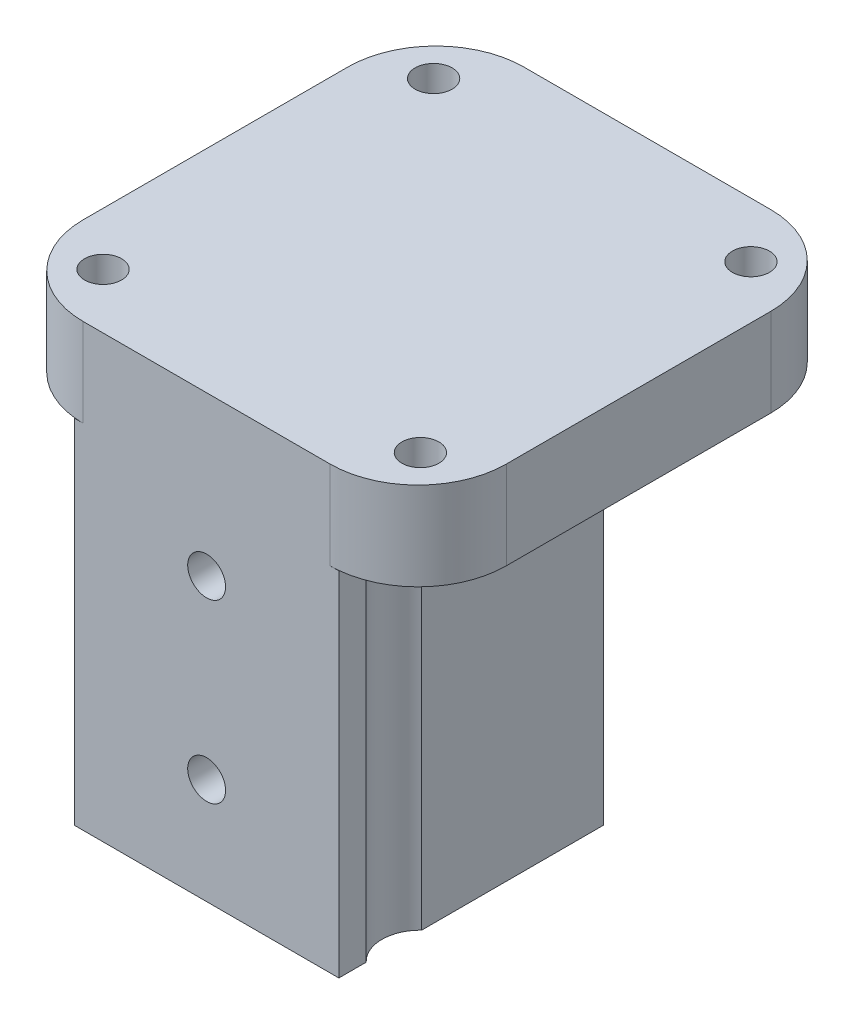
SolidWorks part; units mm, degrees
ref_plane "Front Plane" through (0, 0, 0) normal (0, 0, 1) x (1, 0, 0)
ref_plane "Top Plane" through (0, 0, 0) normal (0, 1, 0) x (1, 0, 0)
ref_plane "Right Plane" through (0, 0, 0) normal (1, 0, 0) x (0, 0, -1)
sketch "Sketch1" plane through (0, 0, 0) normal (0, 1, 0) x (1, 0, 0)
  line L1 (-14, 25) -> (14, 25)
  line L2 (-24, 15) -> (-24, -15)
  line L3 (-14, -25) -> (14, -25)
  line L4 (24, 15) -> (24, -15)
  line L5 (-24, 25) -> (24, -25) construction
  line L6 (-24, -25) -> (24, 25) construction
  arc A0 (-24, -15) -> (-14, -25) centre (-14, -15) ccw
  arc A1 (14, -25) -> (24, -15) centre (14, -15) ccw
  arc A2 (14, 25) -> (24, 15) centre (14, 15) cw
  arc A3 (-14, 25) -> (-24, 15) centre (-14, 15) ccw
  circle A4 centre (-18, 18.75) radius 2.1
  circle A5 centre (18, 18.75) radius 2.1
  circle A6 centre (18, -18.75) radius 2.1
  circle A7 centre (-18, -18.75) radius 2.1
  point P0 (0, 0)
  dimension "D3" = 10
  dimension "D5" = 4.2
  dimension "D6" = 4.2
  dimension "D7" = 4.2
  dimension "D8" = 4.2
  dimension "D1" = 48
  dimension "D2" = 50
  dimension "D4" = 36
extrude "Boss-Extrude1" add sketch "Sketch1" along normal blind 10
sketch "Sketch6" plane through (0, 0, 0) normal (0, -1, 0) x (-1, 0, 0)
  line L1 (10, -20) -> (-10, -20)
  line L2 (10, -20) -> (10, 0)
  line L3 (10, 0) -> (-10, 0)
  line L4 (-10, -20) -> (-10, 0)
  line L5 (10, -20) -> (-10, 0) construction
  line L6 (10, 0) -> (-10, -20) construction
  line L7 (15, -25) -> (-15, -25)
  line L8 (15, -25) -> (15, 5)
  line L9 (15, 5) -> (-15, 5)
  line L10 (-15, -25) -> (-15, 5)
  line L11 (15, -25) -> (-15, 5) construction
  line L12 (15, 5) -> (-15, -25) construction
  point P0 (0, -10)
  point P5 (0, -10)
  dimension "D1" = 20
  dimension "D2" = 20
  dimension "D3" = 30
  dimension "D4" = 30
  dimension "D5" = 10
extrude "Boss-Extrude5" add sketch "Sketch6" along normal blind 40
sketch "Sketch7" plane through (0, 0, 0) normal (0, -1, 0) x (-1, 0, 0)
  circle A0 centre (-18, -18.75) radius 4.35
  circle A1 centre (18, -18.75) radius 4.35
  dimension "D1" = 8.7
  dimension "D2" = 2
extrude "Cut-Extrude1" cut sketch "Sketch7" along normal through all
sketch "Sketch8" plane through (0, 0, 25) normal (0, 0, 1) x (1, 0, 0)
  circle A0 centre (0, -8) radius 2.15
  circle A1 centre (0, -28) radius 2.15
  dimension "D1" = 4.3
  dimension "D2" = 4.3
  dimension "D3" = 8
  dimension "D4" = 28
extrude "Cut-Extrude2" cut sketch "Sketch8" against normal up to next
fillet "Fillet2" radius 10 1 edges at (0, 0, -5)
